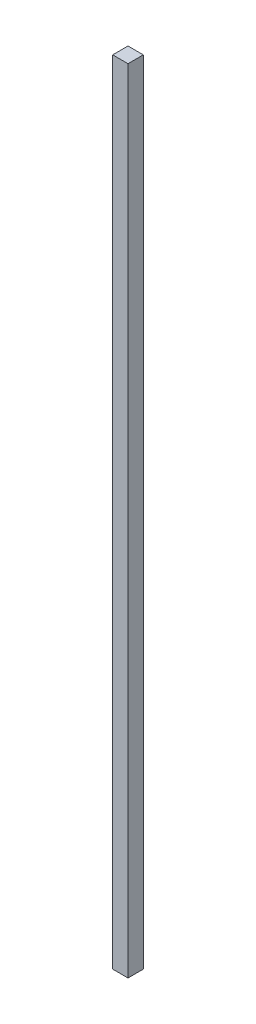
SolidWorks part; units mm, degrees
ref_plane "Plan de face" through (0, 0, 0) normal (0, 0, 1) x (1, 0, 0)
ref_plane "Plan de dessus" through (0, 0, 0) normal (0, 1, 0) x (1, 0, 0)
ref_plane "Plan de droite" through (0, 0, 0) normal (1, 0, 0) x (0, 0, -1)
sketch "Esquisse1" plane through (0, 0, 0) normal (0, 0, 1) x (1, 0, 0)
  line L1 (-20.484, 21.2185) -> (-10.484, 21.2185)
  line L2 (-20.484, 21.2185) -> (-20.484, -495.7815)
  line L3 (-20.484, -495.7815) -> (-10.484, -495.7815)
  line L4 (-10.484, 21.2185) -> (-10.484, -495.7815)
  dimension "D1" = 10
  dimension "D2" = 517
extrude "Boss.-Extru.1" add sketch "Esquisse1" along normal blind 10
equation "\"D2@Esquisse1\"=\"HauteurCoteGauche\" - 23"
equation "\"EpaisseurPlaque\"= 3"
equation "\"ProfondeurBoite\"=460"
equation "\"LongueurSyphon\"=170"
equation "\"LargeurSyphon\"=120"
equation "\"HauteurCoteDroit\"= 490"
equation "\"HauteurCoteGauche\"= 540"
equation "\"HauteurSolSyphon\"= 300"
equation "\"HauteurSyphon\"=\"HauteurCoteGauche\"-\"HauteurSolSyphon\""
equation "\"LargeurDroite\"=10"
equation "\"LargeurGauche\"=150"
equation "\"LargeurBoite\"= \"LargeurDroite\" + \"LargeurGauche\" + \"LargeurSyphon\""
